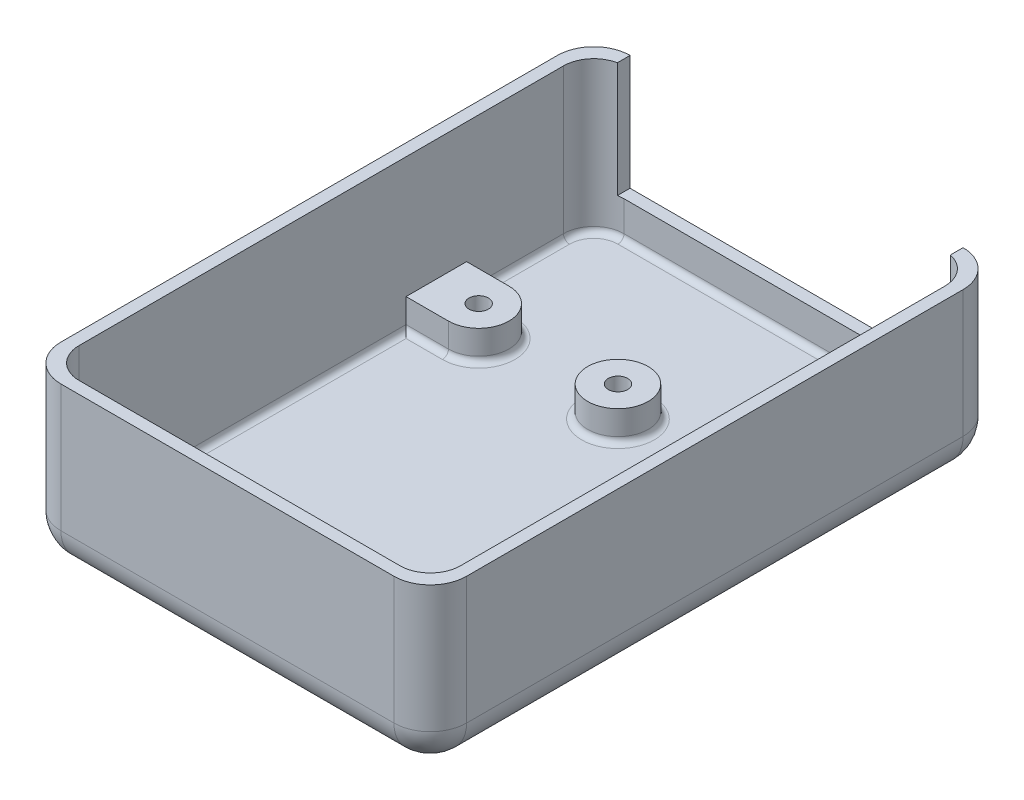
SolidWorks part; units mm, degrees
note: The reader was unsure of these and kept them because the rebuilt part matched: shared geometry of "Эскиз1<3>", "Эскиз1<4>".
ref_plane "Спереди" through (0, 0, 0) normal (0, 0, 1) x (1, 0, 0)
ref_plane "Сверху" through (0, 0, 0) normal (0, 1, 0) x (1, 0, 0)
ref_plane "Справа" through (0, 0, 0) normal (1, 0, 0) x (0, 0, -1)
sketch "Эскиз1" plane through (0, 0, 0) normal (0, 1, 0) x (1, 0, 0)
  line L0 (-9, -8) -> (-9, 86)
  line L1 (-7, -6) -> (56, -6)
  line L2 (-7, -6) -> (-7, 84)
  line L3 (-7, 84) -> (56, 84)
  line L4 (56, -6) -> (56, 84)
  line L5 (-9, 86) -> (58, 86)
  line L6 (58, -8) -> (58, 86)
  line L7 (-9, -8) -> (58, -8)
  line L8 (0, 5) -> (-7, 5)
  line L9 (5, 0) -> (5, -6)
  line L10 (49, 5) -> (56, 5)
  line L11 (44, 0) -> (44, -6)
  line L12 (18, 0) -> (18, -6)
  line L13 (28, 0) -> (28, -6)
  line L14 (0, 63) -> (-7, 63)
  line L15 (0, 53) -> (-7, 53)
  line L16 (49, 63) -> (56, 63)
  line L17 (49, 53) -> (56, 53)
  circle A0 centre (0, 0) radius 1.6
  circle A1 centre (49, 0) radius 1.6
  circle A2 centre (49, 58) radius 1.6
  circle A3 centre (0, 58) radius 1.6
  arc A6 (5, 0) -> (0, 5) centre (0, 0) ccw
  circle A7 centre (23, 58) radius 1.6
  circle A8 centre (23, 0) radius 1.6
  arc A10 (49, 5) -> (44, 0) centre (49, 0) ccw
  arc A11 (28, 0) -> (18, 0) centre (23, 0) ccw
  arc A12 (0, 53) -> (0, 63) centre (0, 58) ccw
  circle A13 centre (23, 58) radius 5
  arc A14 (49, 63) -> (49, 53) centre (49, 58) ccw
  dimension "D1" = 2
  dimension "D9" = 3.2
  dimension "D10" = 90
  dimension "D11" = 23
  dimension "D12" = 26
  dimension "D13" = 58
  dimension "D7" = 5
  dimension "D4" = 7
  dimension "D5" = 6
  dimension "D6" = 7
  dimension "D8" = 2
  dimension "D2" = 2
  dimension "D3" = 2
extrude "Бобышка-Вытянуть1" add sketch "Эскиз1" against normal blind 2 contours A14 L16 L4 L3 L2 L14 A13 L15 L8 A6 L9 L1 L12 L13 L11 L10 L17 | L15 A13 L14 L2 A3 | A13 A7 | L16 A14 L17 L4 A2 | L10 A13 L11 L1 L4 A1 | L13 A13 L12 L1 A8 | L9 A6 L8 L2 L1 A0 | L0 L7 L6 L5 L4 L1 L2 L3
extrude "Бобышка-Вытянуть2" add sketch "Эскиз1<3>" along normal blind 25 contours L0 L7 L6 L5 L4 L1 L2 L3
sketch "Эскиз1<3>" plane through (0, 0, 0) normal (0, 1, 0) x (1, 0, 0) same geometry as "Эскиз1"
extrude "Бобышка-Вытянуть3" add sketch "Эскиз1<4>" along normal blind 5 contours L15 A13 L14 L2 A3 | A13 A7 | L16 A14 L17 L4 A2 | L9 A6 L8 L2 L1 A0 | L13 A13 L12 L1 A8 | L10 A13 L11 L1 L4 A1
sketch "Эскиз1<4>" plane through (0, 0, 0) normal (0, 1, 0) x (1, 0, 0) same geometry as "Эскиз1"
sketch "Эскиз2" plane through (0, 0, -86) normal (0, 0, -1) x (-1, 0, 0)
  line L0 (9, 25) -> (-58, 25) construction
  line L1 (-52, 6) -> (3, 6)
  line L2 (-52, 6) -> (-52, 25)
  line L3 (-52, 25) -> (3, 25)
  line L4 (3, 6) -> (3, 25)
  line L5 (-58, -2) -> (-58, 25) construction
  line L6 (9, -2) -> (-58, -2) construction
  dimension "D1" = 55
  dimension "D2" = 6
  dimension "D3" = 8
extrude "Вырез-Вытянуть1" cut sketch "Эскиз2" against normal up to next
fillet "Скругление7" radius 5 4 edges at (56, 12.5, -84) (-7, 12.5, -84) (56, 15, 6) (-7, 15, 6)
fillet "Скругление8" radius 1 25 edges at (23, 0, -5) (45.4645, 0, -3.5355) (5, 0, -58) (23, 0, -53) (52.5, 0, -63) (44, 0, -58) (52.5, 0, -53) (56, 0, -29) (52.5, 0, -5) (44, 0, 3) (36, 0, 6) (28, 0, 3) (18, 0, 3) (11.5, 0, 6) (5, 0, 3) (3.5355, 0, -3.5355) (-3.5, 0, -5) (-7, 0, -29) (-3.5, 0, -53) (-3.5, 0, -63) (-7, 0, -71) (-5.5355, 0, -82.5355) (24.5, 0, -84) (54.5355, 0, -82.5355) (56, 0, -71)
fillet "Скругление9" radius 6 6 edges at (24.5, -2, 8) (-9, -2, -39) (24.5, -2, -86) (58, -2, -39) (-9, 11.5, 8) (58, 11.5, 8)
fillet "Скругление11" radius 6 4 edges at (-7.2426, -0.2426, -84.2426) (56.2426, -0.2426, -84.2426) (-9, 14.5, -86) (58, 14.5, -86)
